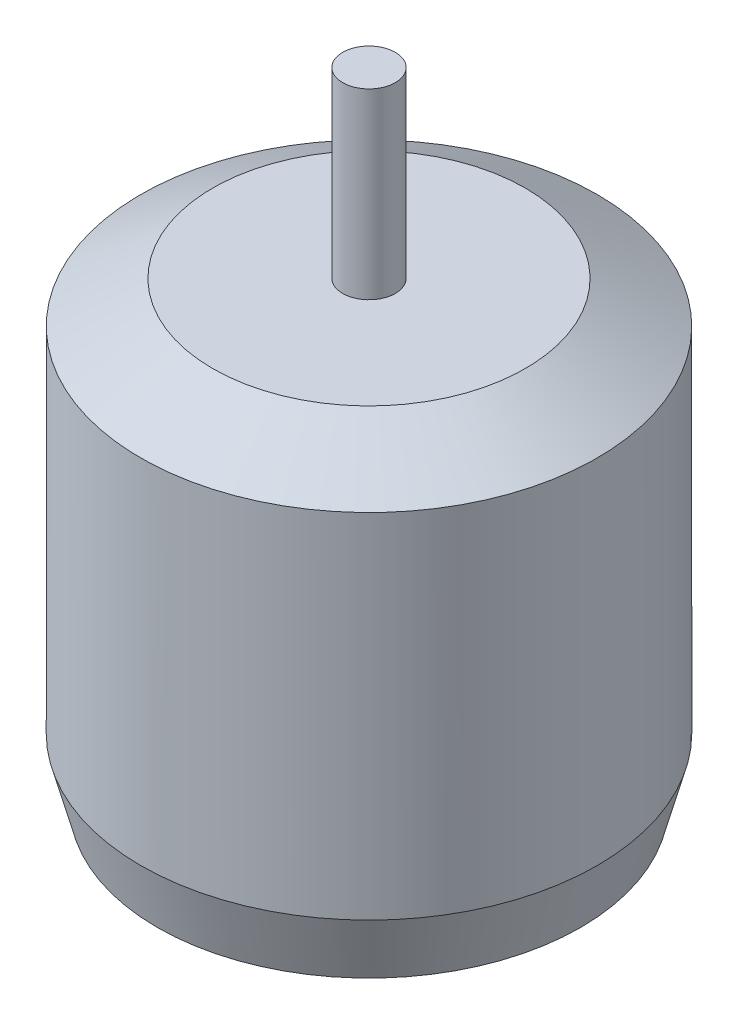
SolidWorks part; units mm, degrees
ref_plane "Front Plane" through (0, 0, 0) normal (0, 0, 1) x (1, 0, 0)
ref_plane "Top Plane" through (0, 0, 0) normal (0, 1, 0) x (1, 0, 0)
ref_plane "Right Plane" through (0, 0, 0) normal (1, 0, 0) x (0, 0, -1)
sketch "Sketch1" plane through (0, 0, 0) normal (0, 1, 0) x (1, 0, 0)
  circle A0 centre (0, 0) radius 13.75
  dimension "D1" = 27.5
extrude "Boss-Extrude1" add sketch "Sketch1" along normal blind 27.5
sketch "Sketch3" plane through (0, 27.5, 0) normal (0, 1, 0) x (1, 0, 0)
  circle A0 centre (0, 0) radius 1.585
  dimension "D1" = 3.17
extrude "Boss-Extrude2" add sketch "Sketch3" along normal blind 11
chamfer "Chamfer1" distance 2.5 angle 60 1 edges at (0, 27.5, 13.75) first distance on face at (0, 27.5, 13.75)
chamfer "Chamfer2" distance 1 angle 75 1 edges at (0, 0, 13.75) first distance on face at (0, 0, 13.75)
sketch "Sketch4" plane through (0, 0, 0) normal (0, -1, 0) x (1, 0, 0)
  line L0 (0, -54.6947) -> (0, 54.6947) construction
  point P0 (0, 10)
  dimension "D1" = 10
hole_wizard "Ø3.0mm Dowel Hole1" positions "Sketch4" profile "Sketch5" hole size "Ø3.0" standard "ANSI Metric"
sketch "Sketch5" plane through (0, 0, 10) normal (1, 0, 0) x (0, 0, -1)
  line L0 (0, 0) -> (0, 3.9013)
  line L1 (0, 3.9013) -> (1.5, 3)
  line L2 (1.5, 3) -> (1.5, 0)
  line L5 (1.5, 0) -> (0, 0)
  line L10 (0, 3.9013) -> (-1.5, 3) construction
  line L11 (0, -6.35) -> (0, 107.95) construction
  dimension "Hole Dia." = 3
  dimension "Hole Depth" = 3
  dimension "Drill Angle" = 118
pattern_circular "CirPattern1" count 4 over 360 about axis through (0, 0, 0) along (0, -1, 0) of "Ø3.0mm Dowel Hole1"
